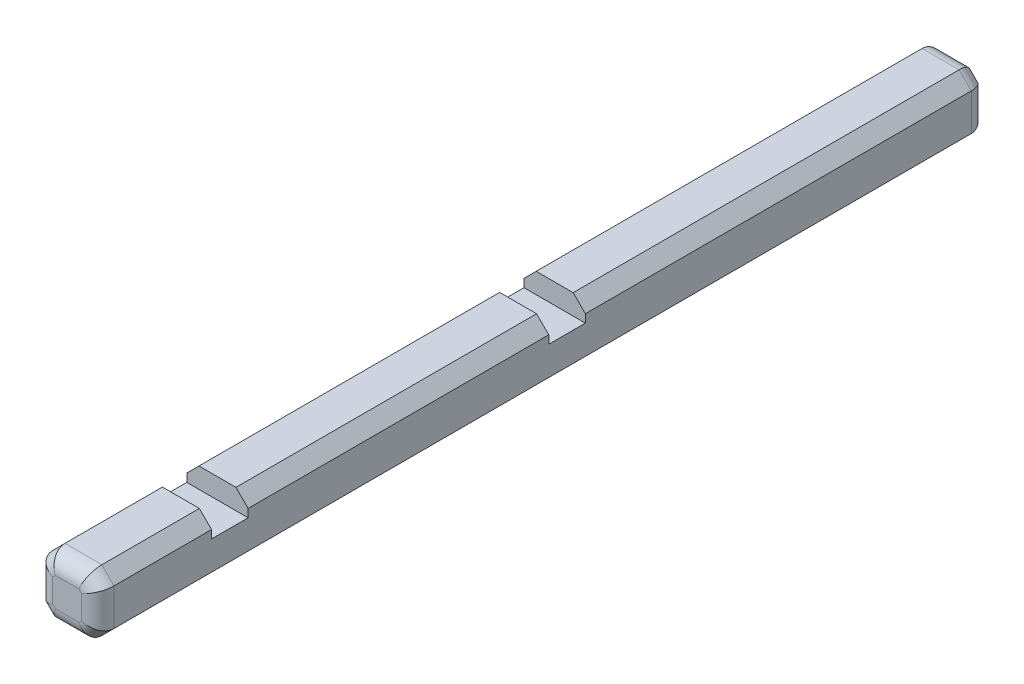
SolidWorks part; units mm, degrees
ref_plane "Front Plane" through (0, 0, 0) normal (0, 0, 1) x (1, 0, 0)
ref_plane "Top Plane" through (0, 0, 0) normal (0, 1, 0) x (1, 0, 0)
ref_plane "Right Plane" through (0, 0, 0) normal (1, 0, 0) x (0, 0, -1)
sketch "Sketch1" plane through (0, 0, 0) normal (0, 0, 1) x (1, 0, 0)
  line L1 (3.775, -3.775) -> (-3.775, -3.775)
  line L2 (3.775, -3.775) -> (3.775, 3.775)
  line L3 (3.775, 3.775) -> (-3.775, 3.775)
  line L4 (-3.775, -3.775) -> (-3.775, 3.775)
  point P0 (0, 3.775)
  point P1 (-3.775, 0)
  dimension "D1" = 7.55
  dimension "D2" = 7.55
extrude "Boss-Extrude1" add sketch "Sketch1" along normal blind 109.5
chamfer "Chamfer2" distance 1.5 angle 45 4 edges at (3.775, -3.775, 54.75) (-3.775, -3.775, 54.75) (3.775, 3.775, 54.75) (-3.775, 3.775, 54.75)
sketch "Sketch2" plane through (0, 0, 0) normal (0, 1, 0) x (1, 0, 0)
  line L0 (2.275, -109.5) -> (-2.275, -109.5) construction
  point P0 (0, -54)
  point P3 (0, -109.5)
  point P5 (0, -95.5)
  dimension "D1" = 55.5
  dimension "D2" = 14
ref_plane "Plane1" through (0, 0, 54) normal (0, 0, -1) x (-1, 0, 0)
sketch "Sketch3" plane through (0, 0, 54) normal (0, 0, -1) x (-1, 0, 0)
  line L0 (-3.775, -2.275) -> (-3.775, 2.275) construction
  line L1 (-3.775, 1.275) -> (3.775, 1.275)
  line L2 (-3.775, 1.275) -> (-3.775, 3.775)
  line L3 (-3.775, 3.775) -> (3.775, 3.775)
  line L4 (3.775, 1.275) -> (3.775, 3.775)
  line L5 (3.775, 2.275) -> (3.775, -2.275) construction
  line L6 (-2.275, 3.775) -> (2.275, 3.775) construction
  dimension "D1" = 2.5
extrude "Cut-Extrude1" cut sketch "Sketch3" along normal blind 4.5
ref_plane "Plane2" through (0, 0, 95.5) normal (0, 0, -1) x (-1, 0, 0)
sketch "Sketch4" plane through (0, 0, 95.5) normal (0, 0, -1) x (-1, 0, 0)
  line L0 (-3.775, -2.275) -> (-3.775, 2.275) construction
  line L1 (-3.775, 1.275) -> (3.775, 1.275)
  line L2 (-3.775, 1.275) -> (-3.775, 3.775)
  line L3 (-3.775, 3.775) -> (3.775, 3.775)
  line L4 (3.775, 1.275) -> (3.775, 3.775)
  line L5 (3.775, 2.275) -> (3.775, -2.275) construction
  line L6 (-2.275, 3.775) -> (2.275, 3.775) construction
  dimension "D1" = 2.5
extrude "Cut-Extrude2" cut sketch "Sketch4" along normal blind 4.5
fillet "Fillet1" radius 2 16 edges at (0, 3.775, 0) (-3.775, 0, 0) (0, -3.775, 0) (3.775, 0, 0) (-3.775, 0, 109.5) (0, 3.775, 109.5) (3.775, 0, 109.5) (0, -3.775, 109.5) (3.025, 3.025, 0) (-3.025, 3.025, 0) (-3.025, -3.025, 0) (3.025, -3.025, 0) (-3.025, -3.025, 109.5) (-3.025, 3.025, 109.5) (3.025, 3.025, 109.5) (3.025, -3.025, 109.5)
equation "\"thiccness\"=4.5"
equation "\"D1@Cut-Extrude1\"=\"thiccness\""
equation "\"cut\"=2.5"
equation "\"D1@Sketch4\"=\"cut\""
equation "\"D1@Cut-Extrude2\"=\"thiccness\""
equation "\"D1@Sketch3\"=\"cut\""
